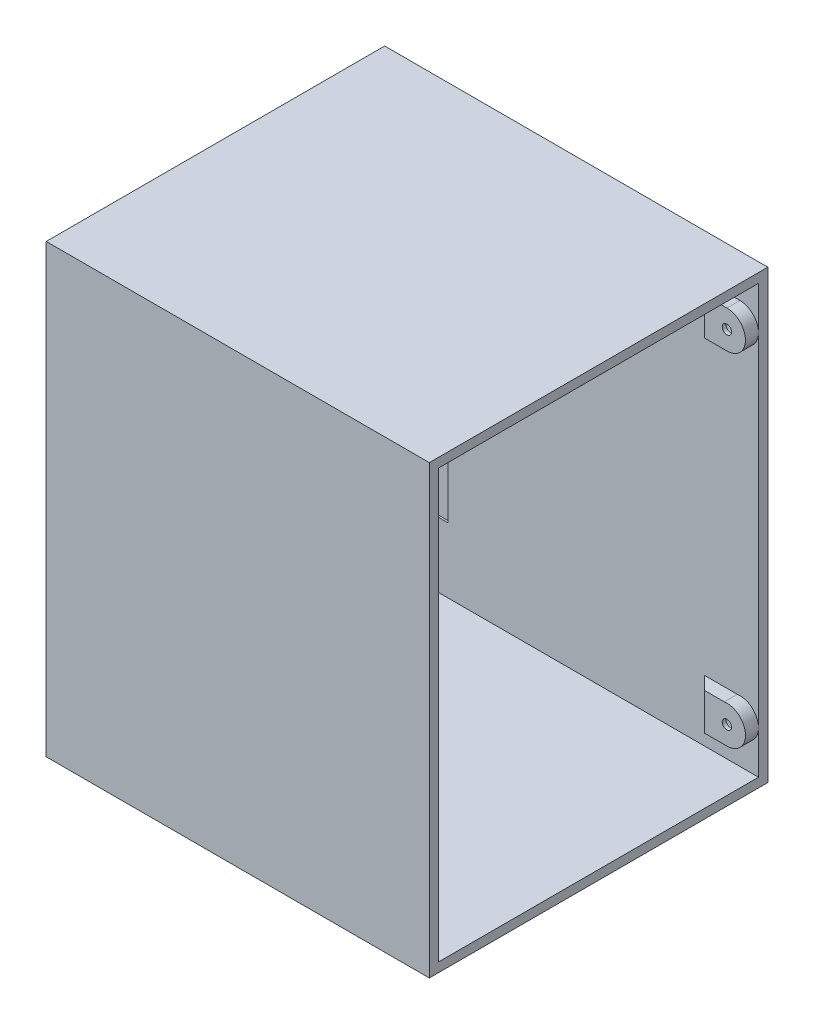
SolidWorks part; units mm, degrees
ref_plane "Front Plane" through (0, 0, 0) normal (0, 0, 1) x (1, 0, 0)
ref_plane "Top Plane" through (0, 0, 0) normal (0, 1, 0) x (1, 0, 0)
ref_plane "Right Plane" through (0, 0, 0) normal (1, 0, 0) x (0, 0, -1)
sketch "Sketch1" plane through (205.5525, 0, 0) normal (1, 0, 0) x (0, 0, -1)
  line L0 (1.5129, 48.8646) -> (1.513, -71.1354) construction
  line L1 (-89.4871, 48.8644) -> (1.5129, 48.8646) construction
  line L2 (-89.4871, 48.8644) -> (-89.487, -71.1356) construction
  line L3 (-89.487, -71.1356) -> (1.513, -71.1354) construction
  line L4 (1.5129, 48.8646) -> (1.513, -71.1354)
  line L5 (-89.4871, 48.8644) -> (1.5129, 48.8646)
  line L6 (-89.4871, 48.8644) -> (-89.487, -71.1356)
  line L7 (-89.487, -71.1356) -> (1.513, -71.1354)
  line L8 (-86.987, -68.6356) -> (-0.987, -68.6355)
  line L9 (-0.9871, 46.3645) -> (-0.987, -68.6355)
  line L10 (-86.9871, 46.3644) -> (-0.9871, 46.3645)
  line L11 (-86.9871, 46.3644) -> (-86.987, -68.6356)
  dimension "D1" = 2.5
extrude "Boss-Extrude1" add sketch "Sketch1" along normal up to surface (103 mm away)
sketch "Sketch2" plane through (0, 0, 86.9871) normal (0, 0, -1) x (-1, 0, 0)
  line L0 (-205.5525, 46.3645) -> (-205.5525, -68.6355) construction
  line L1 (-208.4525, -46.1353) -> (-206.5525, -46.1353)
  line L2 (-208.4525, -46.1353) -> (-208.4525, -40.1355)
  line L3 (-208.4525, -40.1355) -> (-206.5525, -40.1355)
  line L4 (-206.5525, -46.1353) -> (-206.5525, -40.1355)
  line L5 (-206.5525, 23.8645) -> (-208.4525, 23.8645)
  line L6 (-206.5525, 23.8645) -> (-206.5525, 17.8647)
  line L7 (-206.5525, 17.8647) -> (-208.4525, 17.8647)
  line L8 (-208.4525, 23.8645) -> (-208.4525, 17.8647)
  dimension "D1" = 0.1
  dimension "D2" = 1
  dimension "D3" = 0.1
  dimension "D4" = 1
  dimension "D5" = 0
  dimension "D6" = 0
  dimension "D7" = 0
  dimension "D8" = 0
extrude "Boss-Extrude2" add sketch "Sketch2" along normal offset from surface (1.3 mm away) 0.2
sketch "Sketch3" plane through (0, 0, 0.9871) normal (0, 0, 1) x (1, 0, 0)
  line L1 (210.0525, 28.8645) -> (225.0525, 28.8645)
  line L2 (210.0525, 28.8645) -> (210.0525, -51.1355)
  line L3 (210.0525, -51.1355) -> (225.0525, -51.1355)
  line L4 (225.0525, 28.8645) -> (225.0525, -51.1355)
  line L6 (205.5525, -68.6355) -> (205.5525, 46.3645) construction
  line L7 (308.5525, -71.1355) -> (205.5525, -71.1355) construction
  line L8 (308.5525, 48.8645) -> (205.5525, 48.8645) construction
  dimension "D1" = 4.5
  dimension "D2" = 15
  dimension "D3" = 20
  dimension "D4" = 20
extrude "Cut-Extrude1" cut sketch "Sketch3" against normal blind 0.5
sketch "Sketch4" plane through (0, 0, 0.9871) normal (0, 0, 1) x (1, 0, 0)
  line L0 (211.5525, 39.8645) -> (205.5525, 39.8645)
  line L1 (205.5525, -68.6355) -> (205.5525, 46.3645) construction
  line L2 (211.5525, 29.8645) -> (205.5525, 29.8645)
  line L3 (205.5525, 29.8645) -> (205.5525, 39.8645)
  line L4 (211.5525, -52.1355) -> (205.5525, -52.1355)
  line L5 (211.5525, -62.1355) -> (205.5525, -62.1355)
  line L6 (205.5525, -62.1355) -> (205.5525, -52.1355)
  line L7 (303.5525, -62.1355) -> (293.5525, -62.1355)
  line L8 (293.5525, -62.1355) -> (293.5525, -52.1855)
  line L9 (303.6025, -52.1855) -> (293.5525, -52.1855)
  line L10 (303.5525, 29.8645) -> (293.5525, 29.8645)
  line L11 (303.5525, 39.8645) -> (293.5525, 39.8645)
  line L12 (293.5525, 39.8645) -> (293.5525, 29.8645)
  circle A0 centre (211.5525, 34.8645) radius 2.25 construction
  circle A1 centre (211.5525, -57.1355) radius 2.25 construction
  circle A2 centre (211.5525, 34.8645) radius 2.25 construction
  circle A3 centre (211.5525, -57.1355) radius 2.25 construction
  circle A4 centre (211.5525, -57.1355) radius 5
  circle A5 centre (211.5525, 34.8645) radius 5
  circle A6 centre (211.5525, -57.1355) radius 3.5
  circle A7 centre (211.5525, 34.8645) radius 3.5
  circle A8 centre (211.5525, 34.8645) radius 1.25
  circle A9 centre (211.5525, -57.1355) radius 1.25
  circle A10 centre (303.5525, 34.8645) radius 1.6 construction
  circle A11 centre (303.5525, -57.1355) radius 1.6 construction
  circle A12 centre (303.5525, 34.8645) radius 1.6 construction
  circle A13 centre (303.5525, -57.1355) radius 1.6 construction
  circle A14 centre (303.5525, 34.8645) radius 5
  circle A15 centre (303.5525, -57.1355) radius 5
  circle A16 centre (303.5525, -57.1355) radius 3.5
  circle A17 centre (303.5525, -57.1355) radius 1.25
  circle A18 centre (303.5525, 34.8645) radius 3.5
  circle A19 centre (303.5525, 34.8645) radius 1.25
  line M7 (205.5525, 46.3645) -> (205.5525, -68.6355)
  dimension "D1" = 10
  dimension "D2" = 10
  dimension "D3" = 7
  dimension "D4" = 7
  dimension "D5" = 2.5
  dimension "D6" = 2.5
  dimension "D7" = 10
  dimension "D8" = 7
  dimension "D9" = 2.5
  dimension "D10" = 10
  dimension "D11" = 7
  dimension "D12" = 2.5
  dimension "D13" = 10
  dimension "D14" = 10
extrude "Boss-Extrude3" add sketch "Sketch4" along normal up to surface (3.5 mm away) contours A5 A7 | A4 A6 | A5 L0 L2 M7 | A4 L4 L5 M7 | A15 A16 | A14 A18 | A14 L11 L12 L10 | A15 L9 L8 L7 region at (206.4359, 34.8645, 0.9871) region at (208.5525, -52.2521, 0.9871) region at (214.988, 38.3001, 0.9871) region at (214.988, -53.6999, 0.9871) region at (298.7061, -57.479, 0.9871) region at (296.6787, -57.1748, 0.9871) region at (296.6915, 34.8645, 0.9871) region at (298.6939, 34.8645, 0.9871)
extrude "Boss-Extrude4" add sketch "Sketch4<3>" against normal blind 1 from surface contours A7 A8 | A18 A19 | A16 A17 | A6 A9 region at (208.1515, -57.1355, 0.9871) region at (208.1515, 34.8645, 0.9871) region at (300.1515, -57.1355, 0.9871) region at (300.1515, 34.8645, 0.9871) starting at face at (307.0525, 34.8645, 4.4871)
sketch "Sketch4<3>" plane through (0, 0, 0.9871) normal (0, 0, 1) x (1, 0, 0) same geometry as "Sketch4"
extrude "Cut-Extrude2" cut sketch "Sketch4<4>" against normal through all contours A6 A9 | A9 | A7 A8 | A8 | A17 | A16 A17 | A19 | A18 A19 region at (208.1515, -57.1355, 0.9871) region at (208.1515, 34.8645, 0.9871) region at (211.5525, 34.8645, 0.9871) region at (211.5525, -57.1355, 0.9871) region at (300.1515, -57.1355, 0.9871) region at (303.5525, -57.1355, 0.9871) region at (300.1515, 34.8645, 0.9871) region at (303.5525, 34.8645, 0.9871)
sketch "Sketch4<4>" plane through (0, 0, 0.9871) normal (0, 0, 1) x (1, 0, 0) same geometry as "Sketch4"
chamfer "Chamfer1" distance 4 angle 45 1 edges at (293.5525, -57.1605, 4.4871)
chamfer "Chamfer2" distance 4 angle 45 1 edges at (293.5525, 34.8645, 4.4871)
equation "\"R\"=9.03994"
equation "\"R_MOUNT_OUTER\"=10"
equation "\"D1@Sketch4\"=\"R_MOUNT_OUTER\""
equation "\"D2@Sketch4\"=\"R_MOUNT_OUTER\""
equation "\"R_MOUNT_INNER\"=7"
equation "\"D3@Sketch4\"=\"R_MOUNT_INNER\""
equation "\"D4@Sketch4\"=\"R_MOUNT_INNER\""
equation "\"R_SCREW\"=2.5"
equation "\"D5@Sketch4\"=\"R_SCREW\""
equation "\"D6@Sketch4\"=\"R_SCREW\""
equation "\"D7@Sketch4\"=\"R_MOUNT_OUTER\""
equation "\"D8@Sketch4\"=\"R_MOUNT_INNER\""
equation "\"D9@Sketch4\"=\"R_SCREW\""
equation "\"D10@Sketch4\"=\"R_MOUNT_OUTER\""
equation "\"D11@Sketch4\"=\"R_MOUNT_INNER\""
equation "\"D12@Sketch4\"=\"R_SCREW\""
